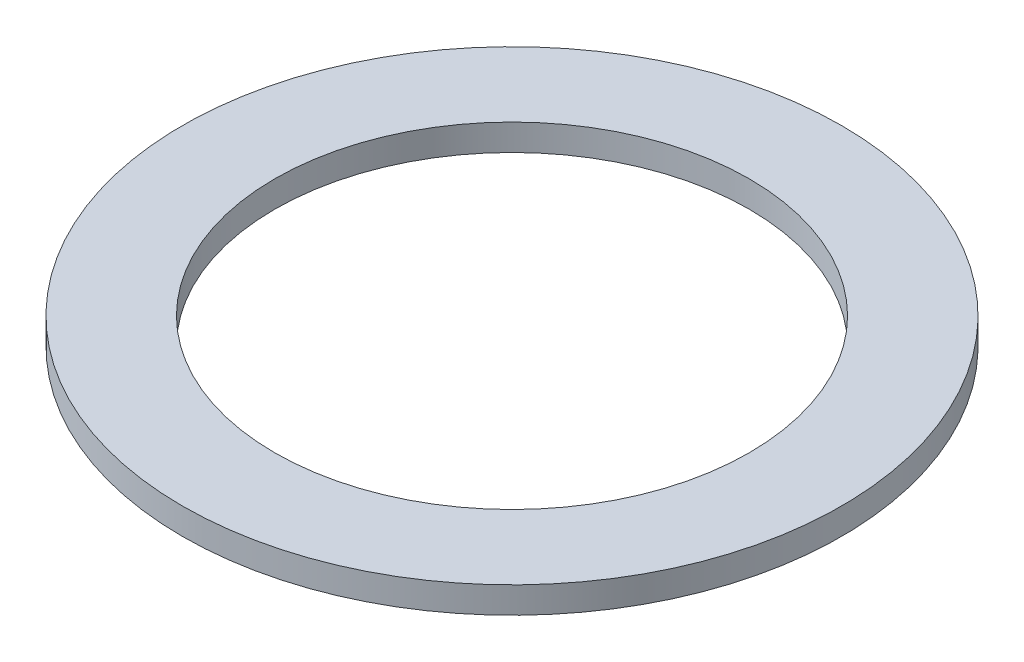
SolidWorks part; units mm, degrees
ref_plane "Front Plane" through (0, 0, 0) normal (0, 0, 1) x (1, 0, 0)
ref_plane "Top Plane" through (0, 0, 0) normal (0, 1, 0) x (1, 0, 0)
ref_plane "Right Plane" through (0, 0, 0) normal (1, 0, 0) x (0, 0, -1)
sketch "Sketch1" plane through (0, 0, 0) normal (0, 1, 0) x (1, 0, 0)
  circle A0 centre (0, 0) radius 62.5
  dimension "FLANGE_OD" = 125
extrude "Boss-Extrude1" add sketch "Sketch1" along normal blind 5
sketch "Sketch2" plane through (0, 0, 0) normal (0, 1, 0) x (1, 0, 0)
  circle A0 centre (0, 0) radius 45
  dimension "BORE_D" = 90
extrude "Cut-Extrude1" cut sketch "Sketch2" along normal through all
sketch "Sketch3" plane through (0, 5, 0) normal (0, 1, 0) x (1, 0, 0)
  circle A0 centre (0, 0) radius 25.4353 construction
  circle A1 centre (-25.4353, 0) radius 1.6623
  dimension "BOLT_D" = 3.3246
  dimension "BOLT_PCD" = 50.8706
extrude "Cut-Extrude2" cut sketch "Sketch3" against normal blind 4.7416 rebuild error yes
pattern_circular "CirPattern1" count 3 over 360 rebuild error yes
